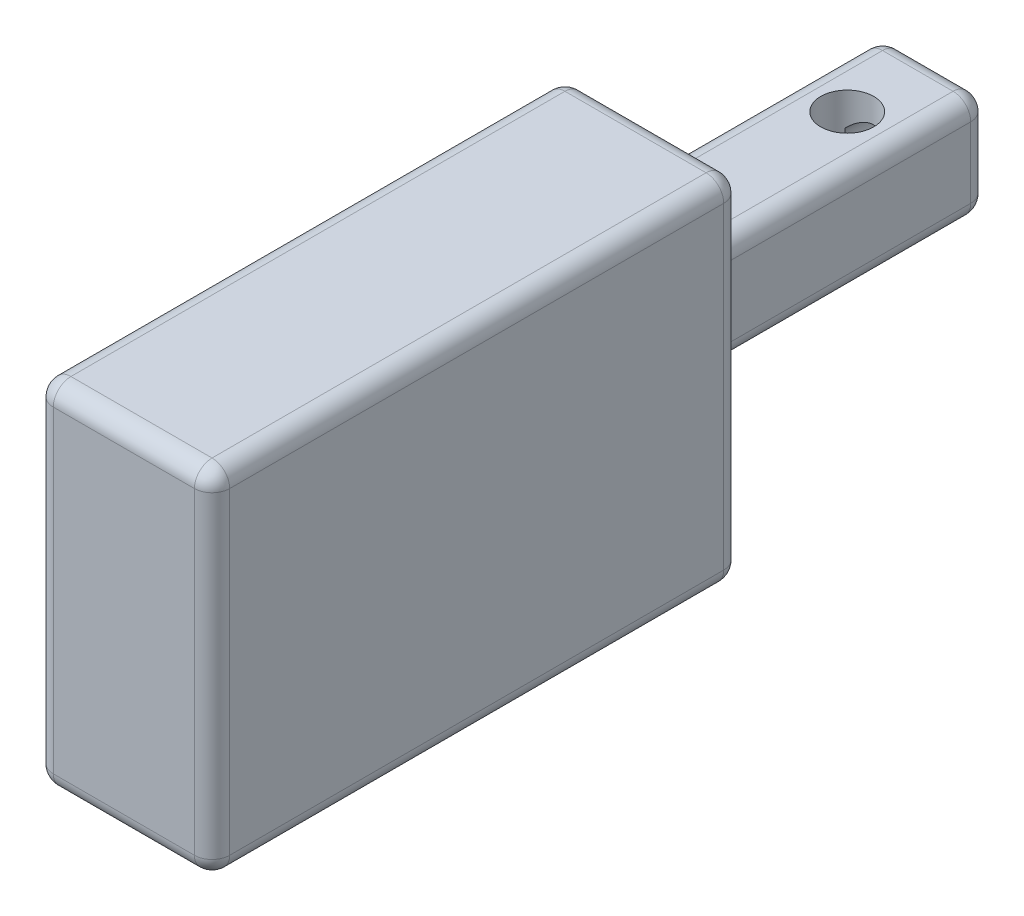
SolidWorks part; units mm, degrees
ref_plane "Front Plane" through (0, 0, 0) normal (0, 0, 1) x (1, 0, 0)
ref_plane "Top Plane" through (0, 0, 0) normal (0, 1, 0) x (1, 0, 0)
ref_plane "Right Plane" through (0, 0, 0) normal (1, 0, 0) x (0, 0, -1)
sketch "草图1" plane through (0, 0, 0) normal (0, 0, 1) x (1, 0, 0)
  line L1 (0, 0) -> (10, 0)
  line L2 (0, 0) -> (0, 22)
  line L3 (0, 22) -> (10, 22)
  line L4 (10, 0) -> (10, 22)
extrude "凸台-拉伸1" add sketch "草图1" along normal blind 30
sketch "草图2" plane through (0, 0, 0) normal (0, 0, 1) x (1, 0, 0)
  line L1 (2, 15) -> (8, 15)
  line L2 (2, 15) -> (2, 9)
  line L3 (2, 9) -> (8, 9)
  line L4 (8, 15) -> (8, 9)
extrude "凸台-拉伸3" add sketch "草图2" against normal blind 14
sketch "草图3" plane through (0, 9, 0) normal (0, -1, 0) x (-1, 0, 0)
  circle A0 centre (-5, 11) radius 1.5
extrude "切除-拉伸1" cut sketch "草图3" against normal blind 6
sketch "草图6" plane through (0, 22, 0) normal (0, 1, 0) x (1, 0, 0)
  line L1 (0, 0) -> (10, 0)
  line L2 (0, 0) -> (0, -30)
  line L3 (0, -30) -> (10, -30)
  line L4 (10, 0) -> (10, -30)
extrude "切除-拉伸2" cut sketch "草图6" against normal blind 2
sketch "草图7" plane through (0, 0, -14) normal (0, 0, -1) x (-1, 0, 0)
  line L1 (-2, 15) -> (-8, 15)
  line L2 (-2, 15) -> (-2, 9)
  line L3 (-2, 9) -> (-8, 9)
  line L4 (-8, 15) -> (-8, 9)
extrude "凸台-拉伸4" add sketch "草图7" along normal blind 2
sketch "草图8" plane through (0, 0, -16) normal (0, 0, -1) x (-1, 0, 0)
  circle A0 centre (-5, 12) radius 1.6
fillet "圆角1" radius 1 24 edges at (5, 0, 30) (5, 20, 30) (10, 0, 15) (10, 10, 30) (10, 20, 15) (0, 10, 30) (0, 0, 15) (0, 20, 15) (2, 9, -8) (2, 12, -16) (2, 15, -8) (8, 15, -8) (8, 12, -16) (8, 9, -8) (8, 12, 0) (5, 9, 0) (2, 12, 0) (5, 15, 0) (0, 10, 0) (5, 0, 0) (10, 10, 0) (5, 20, 0) (5, 15, -16) (5, 9, -16)
extrude "切除-拉伸3" cut sketch "草图8" against normal blind 4 contours A0
